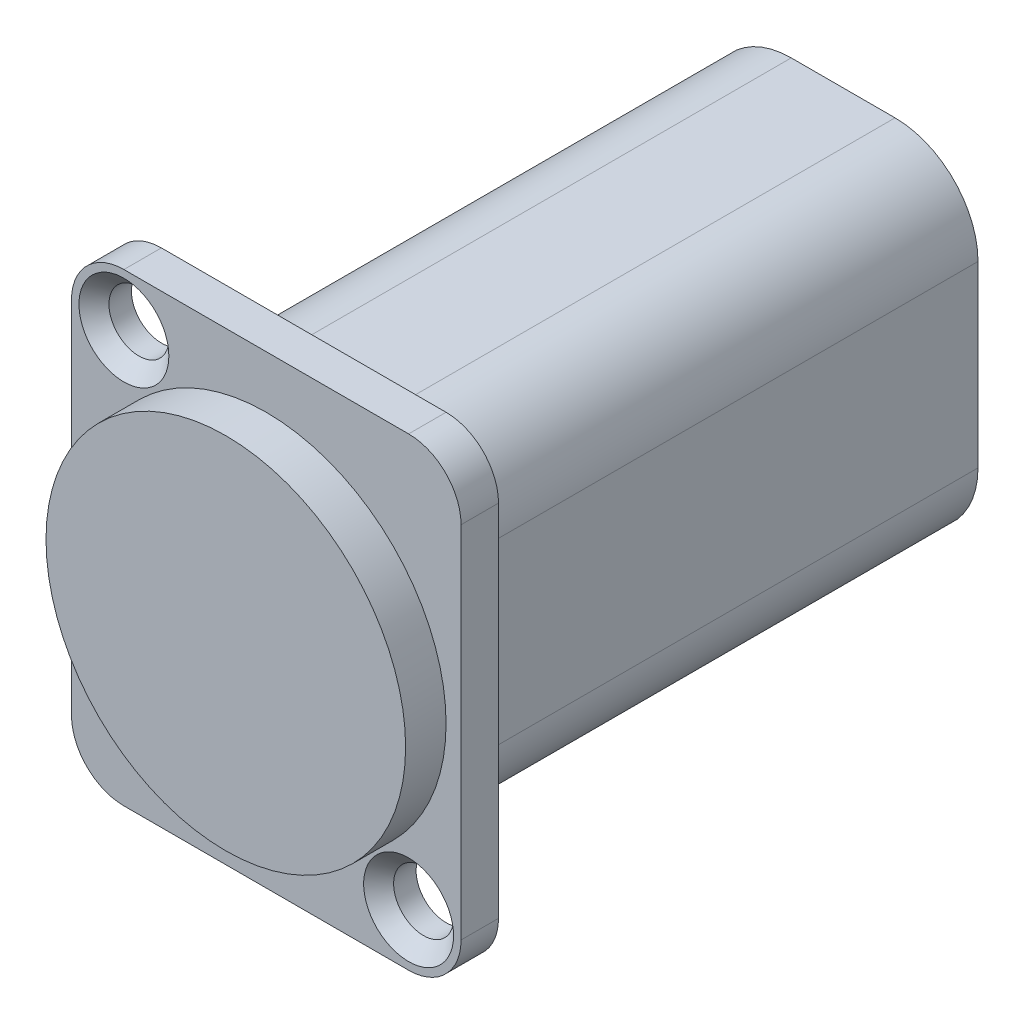
SolidWorks part; units mm, degrees
ref_plane "Front Plane" through (0, 0, 0) normal (0, 0, 1) x (1, 0, 0)
ref_plane "Top Plane" through (0, 0, 0) normal (0, 1, 0) x (1, 0, 0)
ref_plane "Right Plane" through (0, 0, 0) normal (1, 0, 0) x (0, 0, -1)
sketch "Sketch1" plane through (0, 0, 0) normal (0, 0, 1) x (1, 0, 0)
  line L0 (0, 17.2242) -> (0, -16.0013) construction
  line L1 (-9.5, -15.5) -> (9.5, -15.5)
  line L2 (-13, -12) -> (-13, 12)
  line L3 (-9.5, 15.5) -> (9.5, 15.5)
  line L4 (13, -12) -> (13, 12)
  line L5 (-13, -15.5) -> (13, 15.5) construction
  line L6 (-13, 15.5) -> (13, -15.5) construction
  line L7 (-9.5, 12) -> (9.5, -12) construction
  line L9 (-3.4645, -11.5) -> (3.4645, -11.5)
  line L10 (-9, -5.9645) -> (-9, 5.9645)
  line L11 (-3.4645, 11.5) -> (3.4645, 11.5)
  line L12 (9, -5.9645) -> (9, 5.9645)
  line L13 (-9, -11.5) -> (9, 11.5) construction
  line L14 (-9, 11.5) -> (9, -11.5) construction
  circle A0 centre (-9.5, 12) radius 2
  circle A1 centre (9.5, -12) radius 2
  arc A2 (-9, -5.9645) -> (-3.4645, -11.5) centre (-3.4645, -5.9645) ccw
  arc A3 (3.4645, -11.5) -> (9, -5.9645) centre (3.4645, -5.9645) ccw
  arc A4 (9, 5.9645) -> (3.4645, 11.5) centre (3.4645, 5.9645) ccw
  arc A5 (-9, 5.9645) -> (-3.4645, 11.5) centre (-3.4645, 5.9645) cw
  circle A6 centre (0, 0) radius 12
  arc A7 (-9.5, -15.5) -> (-13, -12) centre (-9.5, -12) cw
  arc A8 (9.5, -15.5) -> (13, -12) centre (9.5, -12) ccw
  arc A9 (13, 12) -> (9.5, 15.5) centre (9.5, 12) ccw
  arc A10 (-13, 12) -> (-9.5, 15.5) centre (-9.5, 12) cw
  point P0 (0, 0)
  point P12 (0, 0)
  point P13 (0, 0)
  point P44 (0, 0)
  point P45 (-9.9244, 12.4244)
  dimension "D3" = 4
  dimension "D4" = 19
  dimension "D5" = 24
  dimension "D8" = 1
  dimension "D9" = 24
  dimension "D10" = 1.5
  dimension "D1" = 26
  dimension "D2" = 31
  dimension "D6" = 23
  dimension "D7" = 18
extrude "Boss-Extrude1" add sketch "Sketch1" along normal mid plane 2.5 contours A5 L10 A2 L9 A3 L12 A4 L11 | L1 L4 L3 L2 A1 A0 L10 A5 L11 A4 L12 A3 L9 A2 | L11 A6 | A6 A4 L11 | A3 A6 A4 L12 | A6 L11 A5 | A5 A6 A2 L10 | A6 L9 A3 | L9 A6 | A6 A2 L9 region at (-11.6888, -14.1888, 0) region at (-6.0809, -10.469, 0) region at (0, 0, 0) region at (0, -11.7004, 0) region at (-10.1827, 0, 0) region at (6.0809, -10.469, 0) region at (-6.0809, 10.469, 0) region at (10.1827, 0, 0) region at (0, 11.7004, 0) region at (6.0809, 10.469, 0)
extrude "Boss-Extrude2" add sketch "Sketch1<3>" along normal blind 2.7 from surface contours A5 A6 A2 L10 | L11 A6 | A4 A6 L11 A5 L10 A2 L9 A3 L12 | A3 A6 A4 L12 | L9 A6 region at (0, 0, 0) region at (0, -11.7004, 0) region at (-10.1827, 0, 0) region at (10.1827, 0, 0) region at (0, 11.7004, 0) starting at face at (0, 0, 1.25)
sketch "Sketch1<3>" plane through (0, 0, 0) normal (0, 0, 1) x (1, 0, 0) same geometry as "Sketch1"
extrude "Boss-Extrude3" add sketch "Sketch1<4>" against normal blind 36 from surface contours A6 A4 L11 | A4 A6 L11 A5 L10 A2 L9 A3 L12 | A6 L11 A5 | A6 A2 L9 | A6 L9 A3 region at (-6.0809, -10.469, 0) region at (0, 0, 0) region at (6.0809, -10.469, 0) region at (-6.0809, 10.469, 0) region at (6.0809, 10.469, 0) starting at face at (0, 0, -1.25)
sketch "Sketch1<4>" plane through (0, 0, 0) normal (0, 0, 1) x (1, 0, 0) same geometry as "Sketch1"
chamfer "Chamfer1" distance 1 angle 45 2 edges at (-7.5, 12, 1.25) (11.5, -12, 1.25)
